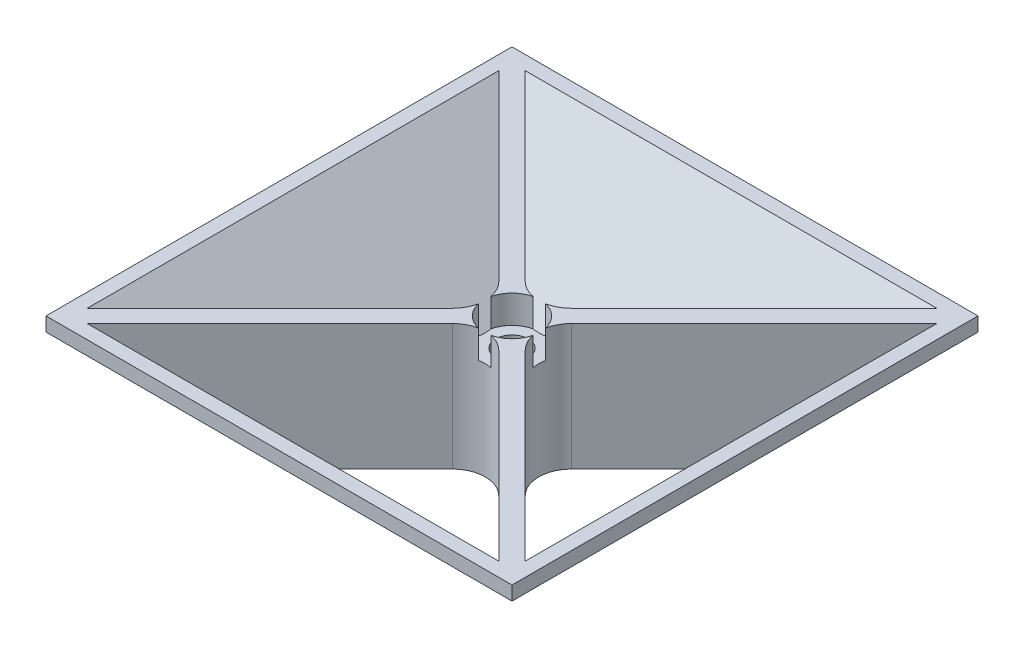
SolidWorks part; units mm, degrees
ref_plane "Front Plane" through (0, 0, 0) normal (0, 0, 1) x (1, 0, 0)
ref_plane "Top Plane" through (0, 0, 0) normal (0, 1, 0) x (1, 0, 0)
ref_plane "Right Plane" through (0, 0, 0) normal (1, 0, 0) x (0, 0, -1)
sketch "Sketch1" plane through (0, 0, 0) normal (0, 1, 0) x (1, 0, 0)
  line L0 (-24.95, 24.95) -> (24.95, 24.95)
  line L1 (-9.95, -9.95) -> (9.95, -9.95)
  line L2 (-9.95, -9.95) -> (-9.95, 9.95)
  line L3 (-9.95, 9.95) -> (9.95, 9.95)
  line L4 (9.95, -9.95) -> (9.95, 9.95)
  line L5 (-9.95, -9.95) -> (9.95, 9.95) construction
  line L6 (-9.95, 9.95) -> (9.95, -9.95) construction
  line L7 (24.95, -24.95) -> (24.95, 24.95)
  line L8 (-24.95, -24.95) -> (24.95, -24.95)
  line L9 (-24.95, -24.95) -> (-24.95, 24.95)
  line L10 (-8.5358, 9.95) -> (9.95, -8.5358)
  line L11 (-9.95, -8.5358) -> (8.5358, 9.95)
  line L12 (-9.95, 8.5358) -> (8.5358, -9.95)
  line L13 (-8.5358, -9.95) -> (9.95, 8.5358)
  line L18 (-10.6571, -9.2429) -> (9.2429, 10.6571) construction
  line L19 (-9.2429, -10.6571) -> (10.6571, 9.2429) construction
  line L20 (-9.2429, 10.6571) -> (10.6571, -9.2429) construction
  line L21 (-10.6571, 9.2429) -> (9.2429, -10.6571) construction
  point P0 (0, 0)
  dimension "D1" = 19.9
  dimension "tamaño" = 15
  dimension "D3" = 1
  dimension "D4" = 1
extrude "Boss-Extrude1" add sketch "Sketch1" along normal blind 15 contours L9 L8 L7 L0 L4 L1 L2 L3 | L2 L12 L11 L10 L3 | L13 L12 L1 L4 L10 | L10 L13 L4 L3 L11 | L1 L13 L12 L11 L2 | L12 L13 L10 L11 region at (0, 0, -24.2443) region at (-5.1541, 0, 5.1541) region at (5.1541, 0, 5.1541) region at (0, 0, 0) region at (-5.1541, 0, -5.1541) region at (5.1541, 0, -5.1541)
chamfer "Chamfer1" distance 13.5 angle 45 4 edges at (-24.95, 0, 0) (0, 0, 24.95) (24.95, 0, 0) (0, 0, -24.95)
chamfer "Chamfer2" distance 13.5 angle 45 4 edges at (0, 15, -9.95) (-9.95, 15, 0) (0, 15, 9.95) (9.95, 15, 0)
fillet "Fillet1" radius 3.5 4 edges at (0, 7.5, 1.4142) (1.4142, 7.5, 0) (0, 7.5, -1.4142) (-1.4142, 7.5, 0)
sketch "Sketch2" plane through (0, 15, 0) normal (0, 1, 0) x (1, 0, 0)
  circle A0 centre (0, 0) radius 3
  circle A1 centre (0, 0) radius 1.75
  dimension "D1" = 6
  dimension "D2" = 3.5
extrude "Cut-Extrude1" cut sketch "Sketch2" against normal blind 3
extrude "Cut-Extrude2" cut sketch "Sketch2<2>" against normal through all contours A1 region at (0, 15, 0)
sketch "Sketch2<2>" plane through (0, 15, 0) normal (0, 1, 0) x (1, 0, 0) same geometry as "Sketch2"
sketch "Sketch3" plane through (0, 0, 0) normal (0, -1, 0) x (1, 0, 0)
  line L0 (-24.95, -24.95) -> (-11.45, -11.45) construction
  line L1 (11.45, 11.45) -> (-11.45, 11.45)
  line L2 (11.45, 11.45) -> (11.45, -11.45)
  line L3 (11.45, -11.45) -> (-11.45, -11.45)
  line L4 (-11.45, 11.45) -> (-11.45, -11.45)
  line L5 (11.45, 11.45) -> (-11.45, -11.45) construction
  line L6 (11.45, -11.45) -> (-11.45, 11.45) construction
  line L8 (-9.95, 9.95) -> (-9.95, -9.95)
  line L9 (9.95, -9.95) -> (-9.95, -9.95)
  line L10 (9.95, 9.95) -> (9.95, -9.95)
  line L11 (9.95, 9.95) -> (-9.95, 9.95)
  point P0 (0, 0)
  circle M5 centre (0, 0) radius 1.75
  line M8 (8.5358, 9.95) -> (2.4749, 3.8891)
  arc M9 (2.4749, 3.8891) -> (-2.4749, 3.8891) centre (0, 6.364) cw
  line M10 (-2.4749, 3.8891) -> (-8.5358, 9.95)
  line M13 (-9.95, 8.5358) -> (-3.8891, 2.4749)
  arc M14 (-3.8891, 2.4749) -> (-3.8891, -2.4749) centre (-6.364, 0) cw
  line M15 (-3.8891, -2.4749) -> (-9.95, -8.5358)
  line M18 (-8.5358, -9.95) -> (-2.4749, -3.8891)
  arc M19 (-2.4749, -3.8891) -> (2.4749, -3.8891) centre (0, -6.364) cw
  line M20 (2.4749, -3.8891) -> (8.5358, -9.95)
  line M23 (9.95, -8.5358) -> (3.8891, -2.4749)
  arc M24 (3.8891, -2.4749) -> (3.8891, 2.4749) centre (6.364, 0) cw
  line M25 (3.8891, 2.4749) -> (9.95, 8.5358)
  dimension "D1" = 1.5
extrude "Cut-Extrude3" cut sketch "Sketch3" against normal blind 1.5 contours L10 L11 L8 L9 M8 M9 M10 M13 M14 M15 M18 M19 M20 M23 M24 M25 M5 region at (-9.2429, 0, 9.6686)
equation "\"D1@Boss-Extrude1\" = \"tamaño@Sketch1\""
equation "\"D1@Chamfer1\"=\"tamaño@Sketch1\"-1.5"
equation "\"D1@Chamfer2\"=\"tamaño@Sketch1\"-1.5"
